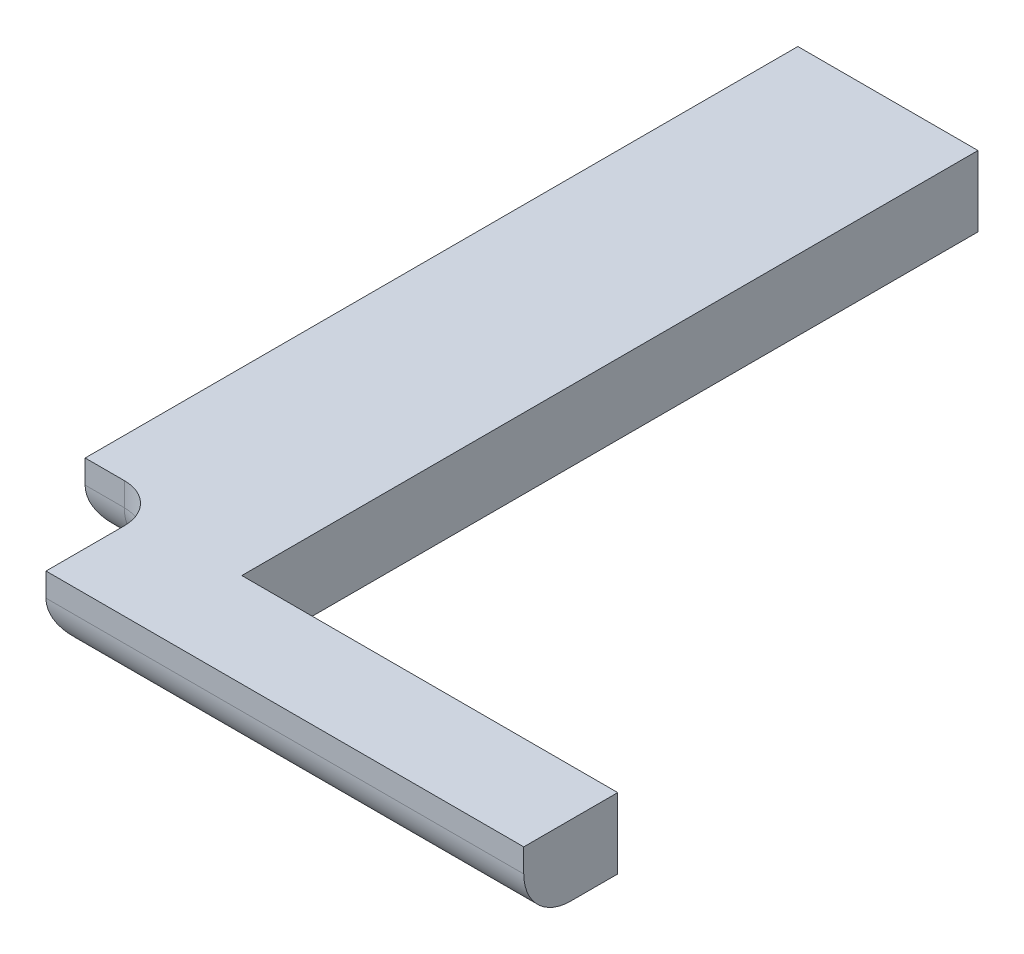
SolidWorks part; units mm, degrees
ref_plane "前基準面" through (0, 0, 0) normal (0, 0, 1) x (1, 0, 0)
ref_plane "上基準面" through (0, 0, 0) normal (0, 1, 0) x (1, 0, 0)
ref_plane "右基準面" through (0, 0, 0) normal (1, 0, 0) x (0, 0, -1)
sketch "草圖1" plane through (0, 0, 0) normal (0, 1, 0) x (1, 0, 0)
  line L0 (0, 0) -> (-48, 0)
  line L1 (-48, 0) -> (-48, 94)
  line L2 (-48, 94) -> (-71, 94)
  line L3 (-71, 94) -> (-71, 3)
  line L4 (-71, 3) -> (-66, 3)
  line L5 (-61, -2) -> (-61, -12)
  line L6 (-61, -12) -> (0, -12)
  line L7 (0, -12) -> (0, 0)
  arc A0 (-66, 3) -> (-61, -2) centre (-66, -2) cw
  dimension "D5" = 5
  dimension "D1" = 48
  dimension "D2" = 94
  dimension "D3" = 23
  dimension "D4" = 5
  dimension "D6" = 10
  dimension "D7" = 12
extrude "填料-伸長1" add sketch "草圖1" along normal blind 9
fillet "圓角1" radius 6 4 edges at (-30.5, 0, 12) (-61, 0, 7) (-62.4645, 0, -1.5355) (-71, 0, -48.5)
sketch "草圖2" plane through (0, 0, 0) normal (0, -1, 0) x (1, 0, 0)
  line L0 (-48, 0) -> (-48, -94) construction
  line L1 (-48, -94) -> (-65, -94) construction
  circle A0 centre (-56, -84) radius 6
  circle A1 centre (-56, -64) radius 6
  dimension "D1" = 12
  dimension "D2" = 20
  dimension "D3" = 8
  dimension "D4" = 8
  dimension "D5" = 10
extrude "除料-伸長1" cut sketch "草圖2" against normal blind 3
